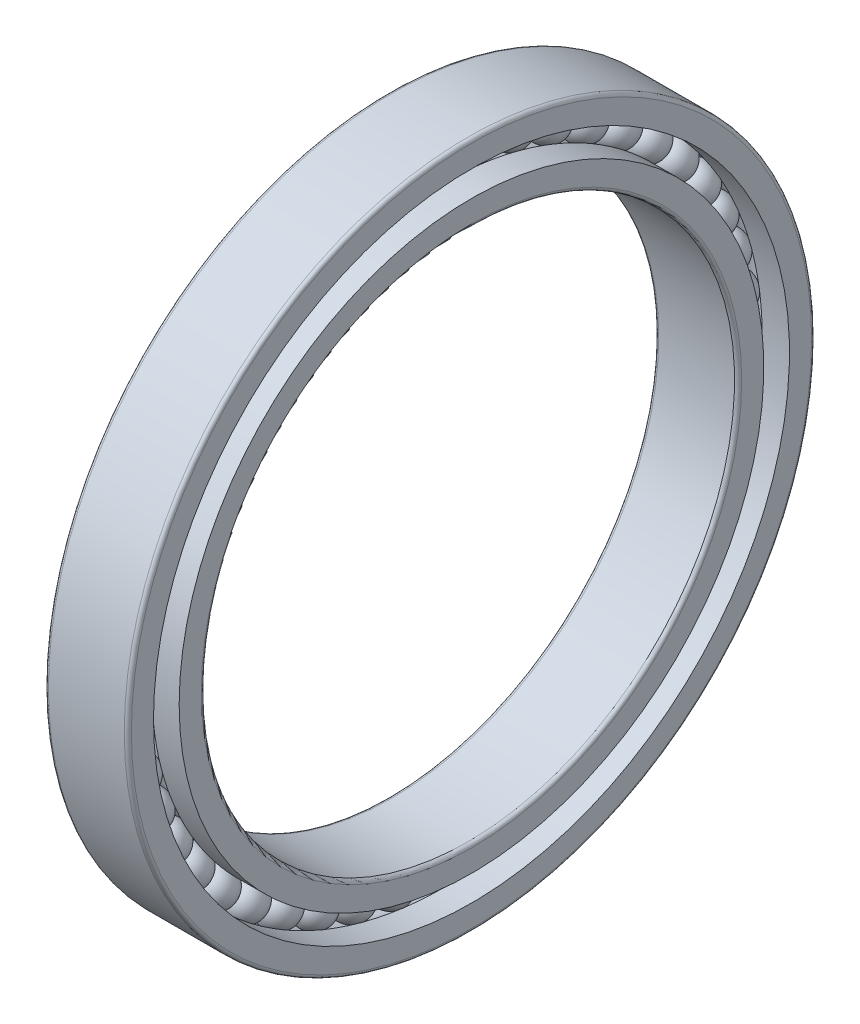
SolidWorks part; units mm, degrees
ref_plane "Front" through (0, 0, 0) normal (0, 0, 1) x (1, 0, 0)
ref_plane "Top" through (0, 0, 0) normal (0, 1, 0) x (1, 0, 0)
ref_plane "Right" through (0, 0, 0) normal (1, 0, 0) x (0, 0, -1)
other "Configuration Table"
sketch "Sketch1" plane through (0, 0, 0) normal (0, 0, 1) x (1, 0, 0)
  line L0 (-9.6833, 0) -> (9.8371, 0) construction
  line L1 (-1.625, 25.75) -> (1.625, 25.75)
  line L2 (-4.5966, 25.75) -> (4.6657, 25.75) construction
  arc A0 (1.625, 25.75) -> (-1.625, 25.75) centre (0, 25.75) ccw
revolve "Revolve1" add sketch "Sketch1" angle 360 about L2
sketch "Sketch2" plane through (0, 0, 0) normal (0, 0, 1) x (1, 0, 0)
  line L0 (-3.5, 24.6667) -> (-3.5, 22.5)
  line L1 (-3.5, 22.5) -> (3.5, 22.5)
  line L2 (3.5, 22.5) -> (3.5, 24.6667)
  line L3 (3.5, 24.6667) -> (1.1978, 24.6667)
  line L4 (-6.9714, 0) -> (8.1665, 0) construction
  line L5 (-6.7058, 25.75) -> (6.7058, 25.75) construction
  line L6 (-1.1978, 24.6667) -> (-3.5, 24.6667)
  arc A0 (-1.1978, 24.6667) -> (1.1978, 24.6667) centre (0, 25.75) ccw
  dimension "B/2" = 3.5
  dimension "D5" = 3.23
  dimension "B" = 7
  dimension "D3" = 25.75
  dimension "D4" = 2.1667
revolve "Revolve2" add sketch "Sketch2" angle 360 about L4
sketch "Sketch3" plane through (0, 0, 0) normal (0, 0, 1) x (1, 0, 0)
  line L0 (-8.7107, 0) -> (9.1288, 0) construction
  line L1 (-3.5, 29) -> (3.5, 29)
  line L2 (-3.5, 29) -> (-3.5, 26.8333)
  line L3 (-3.5, 26.8333) -> (-1.1978, 26.8333)
  line L4 (3.5, 29) -> (3.5, 26.8333)
  line L5 (-7.2948, 25.75) -> (7.2948, 25.75) construction
  line L6 (1.1978, 26.8333) -> (3.5, 26.8333)
  arc A0 (1.1978, 26.8333) -> (-1.1978, 26.8333) centre (0, 25.75) ccw
  dimension "D1" = 3.23
  dimension "D4" = 25.75
  dimension "D5" = 2.1667
  dimension "B/2" = 3.5
  dimension "B" = 7
revolve "Revolve3" add sketch "Sketch3" angle 360 about L0
pattern_circular "Circular-Pattern1" count 48 over 360 about axis through (-6.9714, 0, 0) along (1, 0, 0) of "Revolve1"
fillet "Fillet1" radius 0.3 4 edges at (-3.5, 0, 22.5) (-3.5, 0, 29) (3.5, 0, 29) (3.5, 0, 22.5)
equation "\"d0@Sketch1\" = ( \"DD@Sketch3\" + \"d@Sketch2\" )  / 2"
equation "\"dia@Sketch1\" =  ( \"DD@Sketch3\" - \"d@Sketch2\" )  / 4"
equation "\"D3@Sketch2\" = ( \"DD@Sketch3\" + \"d@Sketch2\" )  / 2 / 2"
equation "\"D4@Sketch2\" = ( \"DD@Sketch3\" - \"d@Sketch2\" )  / 6"
equation "\"D5@Sketch2\" = \"dia@Sketch1\" - 0.02"
equation "\"B/2@Sketch2\" = \"B@Sketch2\" / 2"
equation "\"D4@Sketch3\" = ( \"DD@Sketch3\" + \"d@Sketch2\" )  / 2 / 2"
equation "\"D5@Sketch3\" = ( \"DD@Sketch3\" - \"d@Sketch2\" )  / 6"
equation "\"B@Sketch3\" = \"B@Sketch2\""
equation "\"B/2@Sketch3\" = \"B@Sketch3\" / 2"
equation "\"D1@Sketch3\" = \"dia@Sketch1\" - 0.02"
equation "\"m@Circular-Pattern1\" = int( 3.14159265 / atn(( \"dia@Sketch1\" / 2) / sqr(( \"DD@Sketch3\" + \"d@Sketch2\" )  / 2 * ( \"DD@Sketch3\" + \"d@Sketch2\" )  / 2/4 - ( \"dia@Sketch1\" / 2) *  ( \"dia@Sketch1\" / 2))))-1"
